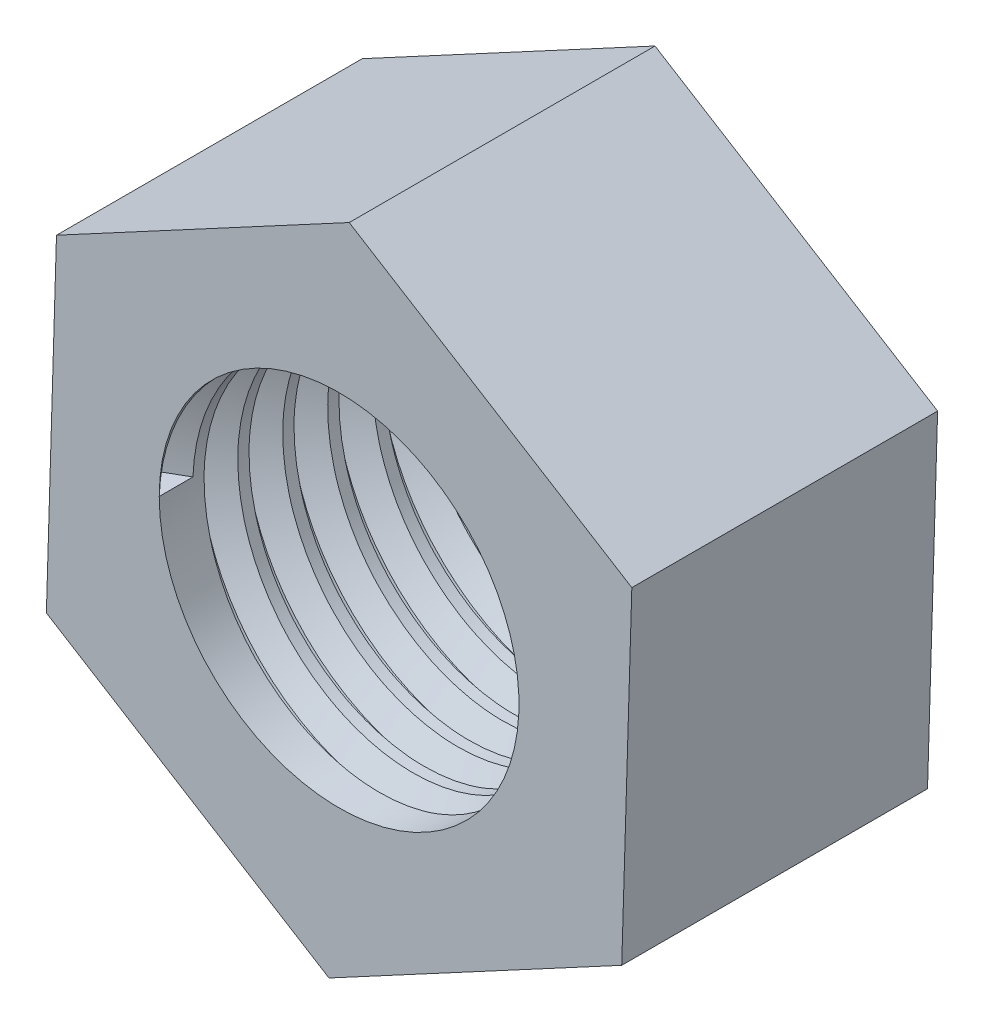
SolidWorks part; units mm, degrees
ref_plane "Front Plane" through (0, 0, 0) normal (0, 0, 1) x (1, 0, 0)
ref_plane "Top Plane" through (0, 0, 0) normal (0, 1, 0) x (1, 0, 0)
ref_plane "Right Plane" through (0, 0, 0) normal (1, 0, 0) x (0, 0, -1)
sketch "Sketch1" plane through (0, 0, 0) normal (0, 0, 1) x (1, 0, 0)
  line L1 (6.2846, -3.8881) -> (6.5095, 3.4986)
  line L2 (6.5095, 3.4986) -> (0.2249, 7.3867)
  line L3 (0.2249, 7.3867) -> (-6.2846, 3.8881)
  line L4 (-6.2846, 3.8881) -> (-6.5095, -3.4986)
  line L5 (-6.5095, -3.4986) -> (-0.2249, -7.3867)
  line L6 (-0.2249, -7.3867) -> (6.2846, -3.8881)
  circle A1 centre (0, 0) radius 6.4 construction
  dimension "D1" = 12.8
extrude "Boss-Extrude1" add sketch "Sketch1" along normal blind 6.8
sketch "Sketch2" plane through (0, 0, 6.8) normal (0, 0, 1) x (1, 0, 0)
  circle A0 centre (0, 0) radius 4
  dimension "D1" = 8
extrude "Cut-Extrude1" cut sketch "Sketch2" against normal through all
thread "Thread1" pitch 1 method cut profile "Thread Profile1" start angle 0, offset 0, length 0, pitch 1, diameter 8
ref_plane "Plane1" through (-4, 0, 6.8) normal (0, -1, 0) x (-1, 0, 0)
sketch "Thread Profile1" plane through (-4, 0, 6.8) normal (0, -1, 0) x (-1, 0, 0)
  line L0 (0, 0) -> (0, 1) construction
  line L1 (0, 0) -> (0.5413, 0.3125)
  line L2 (0.5413, 0.3125) -> (0.5413, 0.4375)
  line L3 (0.5413, 0.4375) -> (0, 0.75)
  line L4 (0.5413, 0.375) -> (0, 0.375) construction
  line L11 (0, 0) -> (0, 0.75)
  point P2 (0, 0)
  dimension "Pitch" = 1
  dimension "Profile_Angle" = 60
  dimension "Profile_Land" = 0.125
  dimension "Profile_Height" = 0.5413
